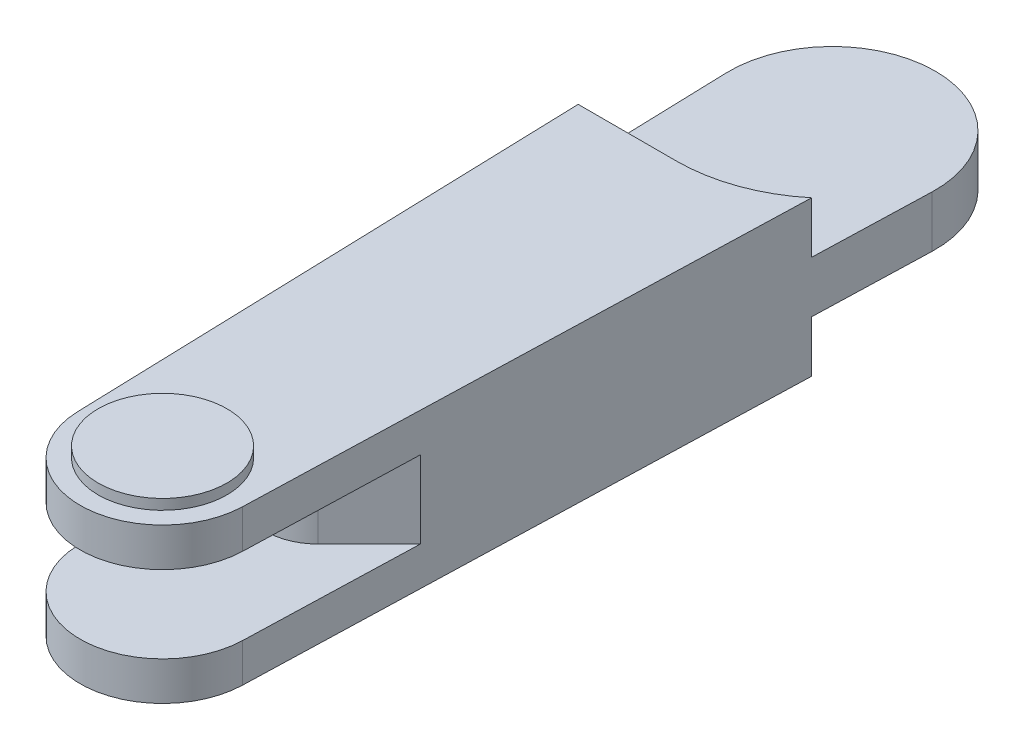
SolidWorks part; units mm, degrees
ref_plane "Front Plane" through (0, 0, 0) normal (0, 0, 1) x (1, 0, 0)
ref_plane "Top Plane" through (0, 0, 0) normal (0, 1, 0) x (1, 0, 0)
ref_plane "Right Plane" through (0, 0, 0) normal (1, 0, 0) x (0, 0, -1)
sketch "Sketch1" plane through (0, 0, 0) normal (0, 1, 0) x (1, 0, 0)
  line L0 (0, 6.5) -> (0, -6.5) construction
  line L1 (-1.5992, -6.5492) -> (-1.9991, 6.4385)
  line L2 (1.5992, -6.5492) -> (1.9991, 6.4385)
  line L3 (0, 0) -> (0, 6.5) construction
  circle A0 centre (0, -6.5) radius 1.5 construction
  circle A1 centre (0, 6.5) radius 1.5 construction
  circle A2 centre (0, 6.5) radius 2
  circle A3 centre (0, -6.5) radius 1.6
  dimension "D2" = 3
  dimension "D3" = 0.1
  dimension "D4" = 0.5
  dimension "D6" = 16.6
  dimension "D7" = 16
  dimension "D5" = 8
  dimension "D1" = 13
extrude "Boss-Extrude1" add sketch "Sketch1" along normal blind 1.5 and the other way blind 1.5 contours A3 | A3 L2 A2 L1 | A2 region at (0, 0, 0.0227) region at (0, 0, 6.5) region at (0, 0, -6.5)
sketch "Sketch2" plane through (0, 1.5, 0) normal (0, 1, 0) x (1, 0, 0)
  circle A0 centre (0, 6.5) radius 2 construction
  circle A1 centre (0, 6.5) radius 3.025
  arc A2 (1.9991, 6.4385) -> (-1.9991, 6.4385) centre (0, 6.5) ccw construction
  dimension "D1" = 6.05
extrude "Cut-Extrude1" cut sketch "Sketch2" against normal blind 1
sketch "Sketch3" plane through (0, -1.5, 0) normal (0, -1, 0) x (1, 0, 0)
  circle A1 centre (0, -6.5) radius 3.025
  circle A2 centre (0, -6.5) radius 3.025
  dimension "D1" = 0
extrude "Cut-Extrude2" cut sketch "Sketch3" against normal blind 1
sketch "Sketch4" plane through (0, 0, 0) normal (0, 1, 0) x (1, 0, 0)
  line L0 (0, -6.5) -> (0, -4.9)
  line L1 (0, -4.9) -> (-163.9469, 159.0469)
  line L2 (0, -4.9) -> (161.9555, 157.0555)
  line L3 (161.9555, 157.0555) -> (161.9555, -6.5)
  line L4 (161.9555, -6.5) -> (0, -6.5)
  line L5 (0, -6.5) -> (-163.9469, -6.5)
  line L6 (-163.9469, -6.5) -> (-163.9469, 159.0469)
  line L7 (161.9555, -6.5) -> (0, -276.85)
  line L8 (0, -276.85) -> (-163.9469, -6.5)
  circle A0 centre (0, -6.5) radius 1.6
  arc A1 (-1.5992, -6.5492) -> (1.5992, -6.5492) centre (0, -6.5) ccw construction
  point P7 (0, -276.85)
  point P13 (-164.0969, 155.6969)
  point P14 (161.9555, 155.6969)
  point P15 (0, 0)
  point P16 (0, -7.9297)
  point P17 (0, -5.2)
  dimension "D1" = 45
  dimension "D2" = 45
extrude "Cut-Extrude3" cut sketch "Sketch4" against normal blind 0.75 and the other way blind 0.75 contours A0 L1 L6 L5 | A0 L4 L3 L2 | L5 A0 L4 | L4 A0 L0 | L0 A0 L5 | A0 L5 L8 L7 L4 region at (-0.6791, 0, 5.8209) region at (0.6791, 0, 5.8209) region at (0, 0, 7.1791) region at (-108.7907, 0, -48.6954) region at (107.4634, 0, -48.0318) region at (-0.6639, 0, 96.6248)
fillet "Fillet1" radius 1 1 edges at (0, 0, 4.9)
sketch "Sketch5" plane through (0, 1.5, 0) normal (0, 1, 0) x (1, 0, 0)
  circle A0 centre (0, -6.5) radius 1.25
  dimension "D1" = 2.5
extrude "Boss-Extrude2" add sketch "Sketch5" along normal blind 0.2
sketch "Sketch6" plane through (0, -1.5, 0) normal (0, -1, 0) x (1, 0, 0)
  circle A1 centre (0, 6.5) radius 1.25
  circle A2 centre (0, 6.5) radius 1.25
  dimension "D1" = 0
extrude "Boss-Extrude3" add sketch "Sketch6" along normal blind 0.2
sketch "Sketch7" plane through (0, 1.5, 0) normal (0, 1, 0) x (1, 0, 0)
  line L0 (0, 3.475) -> (-4.8083, 3.475)
  line L1 (-4.8083, 3.475) -> (-1.9292, 4.17)
  line L2 (0, 0) -> (0, 6.5) construction
  arc A0 (-1.9292, 4.17) -> (1.9292, 4.17) centre (0, 6.5) ccw construction
  arc A1 (-1.9292, 4.17) -> (1.9292, 4.17) centre (0, 6.5) ccw construction
  arc A2 (-1.9292, 4.17) -> (1.9292, 4.17) centre (0, 6.5) ccw
  point P5 (-4.8522, 3.246)
  arc M4 (1.9292, 4.17) -> (-1.9292, 4.17) centre (0, 6.5) cw
  line M5 (-1.9292, 4.17) -> (-1.5992, -6.5492)
extrude "Cut-Extrude4" cut sketch "Sketch7" against normal up to surface (1 mm away) contours L0 L2 A2 M5 | L2 L0 M4 region at (-1.4504, 1.5, -3.6781) up to face at (0, 0.5, -5.6459)
sketch "Sketch8" plane through (0, -1.5, 0) normal (0, -1, 0) x (1, 0, 0)
  line L0 (0, -3.475) -> (-4.8083, -3.475) construction
  line L1 (-4.8083, -3.475) -> (-1.9292, -4.17) construction
  line L2 (0, -3.475) -> (-4.8083, -3.475)
  line L3 (-4.8083, -3.475) -> (-1.9292, -4.17)
  arc A0 (1.9292, -4.17) -> (-1.9292, -4.17) centre (0, -6.5) ccw construction
  arc A1 (1.9292, -4.17) -> (-1.9292, -4.17) centre (0, -6.5) ccw
  line M2 (-1.5992, 6.5492) -> (-1.9292, -4.17)
  arc M3 (-1.9292, -4.17) -> (1.9292, -4.17) centre (0, -6.5) cw
extrude "Cut-Extrude5" cut sketch "Sketch8" against normal up to surface (1 mm away) contours L2 M3 M2 region at (-1.4504, -1.5, -3.6781) up to face at (0, -0.5, -5.6459)
